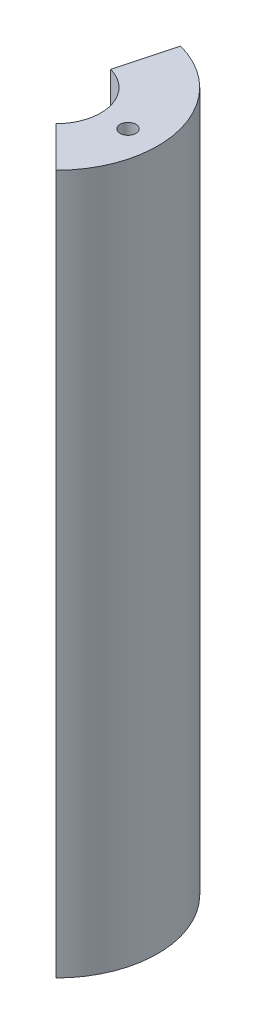
SolidWorks part; units mm, degrees
ref_plane "Front" through (0, 0, 0) normal (0, 0, 1) x (1, 0, 0)
ref_plane "Top" through (0, 0, 0) normal (0, 1, 0) x (1, 0, 0)
ref_plane "Right" through (0, 0, 0) normal (1, 0, 0) x (0, 0, -1)
sketch "Sketch1" plane through (0, 0, 0) normal (0, 1, 0) x (1, 0, 0)
  line L0 (0, 0) -> (-11.3137, 11.3137)
  line L1 (0, 0) -> (11.3137, -11.3137)
  line L2 (0, 0) -> (4.1411, 15.4548)
  circle A0 centre (0, 0) radius 16
  circle A1 centre (0, 0) radius 7
  circle A2 centre (0, 0) radius 11.3137
  circle A3 centre (0, 11.3137) radius 1.25
  circle A4 centre (11.3137, 0) radius 1.25
  dimension "D1" = 120
extrude "Boss-Extrude1" add sketch "Sketch1" along normal blind 110.3 contours A4 A2 L1 A0 L2 | A4 A2 L2 A1 L1 region at (7.3508, 0, -2.0558) region at (11.0008, 0, -3.0082)
